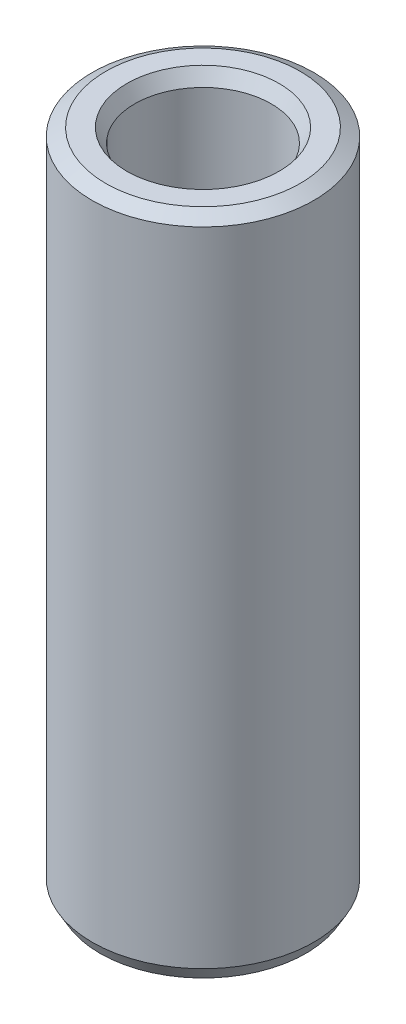
SolidWorks part; units mm, degrees
ref_plane "Front Plane" through (0, 0, 0) normal (0, 0, 1) x (1, 0, 0)
ref_plane "Top Plane" through (0, 0, 0) normal (0, 1, 0) x (1, 0, 0)
ref_plane "Right Plane" through (0, 0, 0) normal (1, 0, 0) x (0, 0, -1)
sketch "Sketch1" plane through (0, 0, 0) normal (0, 1, 0) x (1, 0, 0)
  circle A0 centre (0, 0) radius 47.5
  dimension "SLEEVE_OD" = 95
extrude "Boss-Extrude1" add sketch "Sketch1" along normal blind 284.4884
sketch "Sketch2" plane through (0, 0, 0) normal (0, 1, 0) x (1, 0, 0)
  circle A0 centre (0, 0) radius 29.2455
  dimension "BORE_D" = 58.4911
extrude "Cut-Extrude1" cut sketch "Sketch2" along normal through all
chamfer "Chamfer1" distance 3.3764 angle 60 4 edges at (0, 284.4884, 29.2455) (0, 0, 29.2455) (0, 0, 47.5) (0, 284.4884, 47.5) first distance on face at (0, 284.4884, 29.2455) first distance on face at (0, 0, 29.2455) first distance on face at (0, 284.4884, 47.5)
